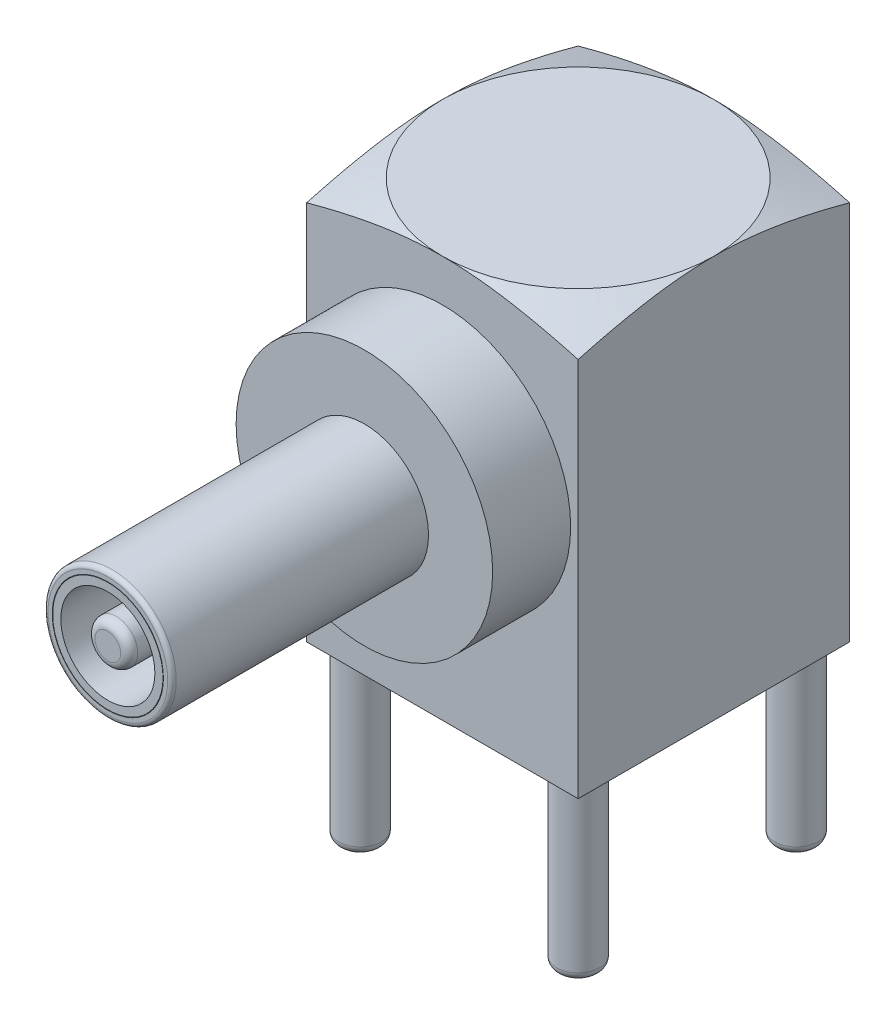
SolidWorks part; units mm, degrees
material "黄铜"
ref_plane "前视基准面" through (0, 0, 0) normal (0, 0, 1) x (1, 0, 0)
ref_plane "上视基准面" through (0, 0, 0) normal (0, 1, 0) x (1, 0, 0)
ref_plane "右视基准面" through (0, 0, 0) normal (1, 0, 0) x (0, 0, -1)
sketch "草图1" plane through (0, 0, 0) normal (0, 1, 0) x (1, 0, 0)
  line L1 (3.175, -3.175) -> (-3.175, -3.175)
  line L2 (3.175, -3.175) -> (3.175, 3.175)
  line L3 (3.175, 3.175) -> (-3.175, 3.175)
  line L4 (-3.175, -3.175) -> (-3.175, 3.175)
  line L5 (3.175, -3.175) -> (-3.175, 3.175) construction
  line L6 (3.175, 3.175) -> (-3.175, -3.175) construction
  circle A0 centre (0, 0) radius 3.175
  point P0 (0, 0)
  dimension "D1" = 6.35
  dimension "D2" = 6.35
sketch "草图2" plane through (0, 0, 0) normal (0, 1, 0) x (1, 0, 0)
  line L4 (-3.175, -3.175) -> (3.175, -3.175)
  line L5 (-3.175, 3.175) -> (-3.175, -3.175)
  line L6 (3.175, 3.175) -> (-3.175, 3.175)
  line L7 (3.175, -3.175) -> (3.175, 3.175)
  line L8 (-3.175, -3.175) -> (3.175, -3.175)
  line L9 (-3.175, 3.175) -> (-3.175, -3.175)
  line L10 (3.175, 3.175) -> (-3.175, 3.175)
  line L11 (3.175, -3.175) -> (3.175, 3.175)
  dimension "D2" = 0
extrude "凸台-拉伸1" add sketch "草图2" along normal blind 9.4
sketch "草图3" plane through (0, 9.4, 0) normal (0, 1, 0) x (1, 0, 0)
  line L0 (0, 0) -> (5.0421, 0)
  line L4 (-3.175, -3.175) -> (3.175, -3.175)
  line L5 (-3.175, 3.175) -> (-3.175, -3.175)
  line L6 (3.175, 3.175) -> (-3.175, 3.175)
  line L7 (3.175, -3.175) -> (3.175, 3.175)
  line L8 (-3.175, -3.175) -> (3.175, -3.175)
  line L9 (-3.175, 3.175) -> (-3.175, -3.175)
  line L10 (3.175, 3.175) -> (-3.175, 3.175)
  line L11 (3.175, -3.175) -> (3.175, 3.175)
  circle A1 centre (0, 0) radius 3.175
  circle A2 centre (0, 0) radius 3.175
  dimension "D1" = 0
  dimension "D2" = 0
sketch "草图5" plane through (0, 0, 0) normal (0, 0, 1) x (1, 0, 0)
  line L0 (3.175, 9.4) -> (5.2489, 14.5885)
  line L1 (0, 9.4) -> (5.0421, 9.4) construction
  line L2 (3.175, 9.4) -> (-3.175, 9.4) construction
  line L5 (3.175, 9.4) -> (5.2489, 8.6042)
  line L6 (5.2489, 8.6042) -> (5.2489, 14.5885)
ref_axis "基准轴1" through (0, 15.4277, 0) along (0, -1, 0)
revolve "切除-旋转1" cut sketch "草图5" angle 360 about axis through (0, 15.4277, 0) along (0, -1, 0)
sketch "草图6" plane through (0, 0, 0) normal (0, 0, 1) x (1, 0, 0)
  line L0 (0, 15.4277) -> (0, -0.7347) construction
  circle A0 centre (0, 5.4167) radius 3
  dimension "D1" = 6
extrude "凸台-拉伸2" add sketch "草图6" along normal blind 5
sketch "草图7" plane through (0, 0, 5) normal (0, 0, 1) x (1, 0, 0)
  circle A0 centre (0, 5.4167) radius 1.5
  circle A1 centre (0, 5.4167) radius 1.3
  dimension "D2" = 2.6
  dimension "D1" = 3
extrude "凸台-拉伸3" add sketch "草图7" along normal blind 6
sketch "Sketch1" plane through (0, 0, 0) normal (0, -1, 0) x (1, 0, 0)
  line L1 (-2.55, -2.55) -> (2.55, -2.55)
  line L2 (-2.55, -2.55) -> (-2.55, 2.55)
  line L3 (-2.55, 2.55) -> (2.55, 2.55)
  line L4 (2.55, -2.55) -> (2.55, 2.55)
  line L5 (-2.55, -2.55) -> (2.55, 2.55) construction
  line L6 (-2.55, 2.55) -> (2.55, -2.55) construction
  circle A0 centre (0, 0) radius 1.5
  circle A1 centre (2.55, 2.55) radius 0.5
  circle A2 centre (2.55, -2.55) radius 0.5
  circle A3 centre (-2.55, -2.55) radius 0.5
  circle A4 centre (-2.55, 2.55) radius 0.5
  circle A5 centre (0, 0) radius 0.5
  point P0 (0, 0)
  point P13 (-10.1472, 1.7049)
  dimension "D3" = 3
  dimension "D8" = 1
  dimension "D1" = 5.1
  dimension "D2" = 5.1
sketch "Sketch2" plane through (0, 0, 0) normal (0, -1, 0) x (1, 0, 0)
  circle A11 centre (0, 0) radius 1.5
  circle A12 centre (0, 0) radius 1.5
  dimension "D6" = 0
extrude "Extrude1" cut sketch "Sketch2" against normal blind 8
sketch "Sketch3" plane through (0, 8, 0) normal (0, -1, 0) x (1, 0, 0)
  circle A0 centre (0, 0) radius 1.49
  dimension "D1" = 2.98
extrude "Extrude3" add sketch "Sketch3" along normal blind 8
extrude "Extrude4" add sketch "Sketch" along normal blind 8
sketch "Sketch" plane through (0, 8, 0) normal (0, -1, 0) x (1, 0, 0) same geometry as "Sketch3"
sketch "Sketch4" plane through (0, 0, 0) normal (0, -1, 0) x (1, 0, 0)
  circle A0 centre (0, 0) radius 0.5
  dimension "D1" = 1
extrude "Extrude5" add sketch "Sketch4" along normal blind 4
sketch "Sketch5" plane through (0, 0, 0) normal (0, -1, 0) x (1, 0, 0)
  circle A3 centre (-2.55, 2.55) radius 0.5
  circle A4 centre (-2.55, 2.55) radius 0.5
  circle A5 centre (-2.55, -2.55) radius 0.5
  circle A6 centre (-2.55, -2.55) radius 0.5
  circle A7 centre (2.55, -2.55) radius 0.5
  circle A8 centre (2.55, -2.55) radius 0.5
  circle A9 centre (2.55, 2.55) radius 0.5
  circle A10 centre (2.55, 2.55) radius 0.5
  dimension "D2" = 0
  dimension "D3" = 0
  dimension "D4" = 0
  dimension "D5" = 0
extrude "Extrude9" add sketch "Sketch5" along normal blind 4
sketch "Sketch6" plane through (0, 0, 5) normal (0, 0, 1) x (1, 0, 0)
  circle A0 centre (0, 5.4167) radius 1.29
  dimension "D1" = 2.58
extrude "Extrude10" add sketch "Sketch6" along normal blind 6
sketch "Sketch7" plane through (0, 0, 11) normal (0, 0, 1) x (1, 0, 0)
  circle A0 centre (0, 5.4167) radius 1.1
extrude "Extrude11" cut sketch "Sketch7" against normal blind 8
sketch "Sketch8" plane through (0, 0, 3) normal (0, 0, 1) x (1, 0, 0)
  circle A0 centre (0, 5.4167) radius 0.5
  dimension "D2" = 1
extrude "Extrude12" add sketch "Sketch8" along normal blind 8
fillet "Fillet1" radius 0.2 1 edges at (0.5, 5.4167, 11)
fillet "Fillet2" radius 0.1 1 edges at (1.5, 5.4167, 11)
fillet "Fillet3" radius 0.2 5 edges at (0, -4, -0.5) (2.55, -4, -3.05) (-2.55, -4, -3.05) (2.55, -4, 2.05) (-2.55, -4, 2.05)
